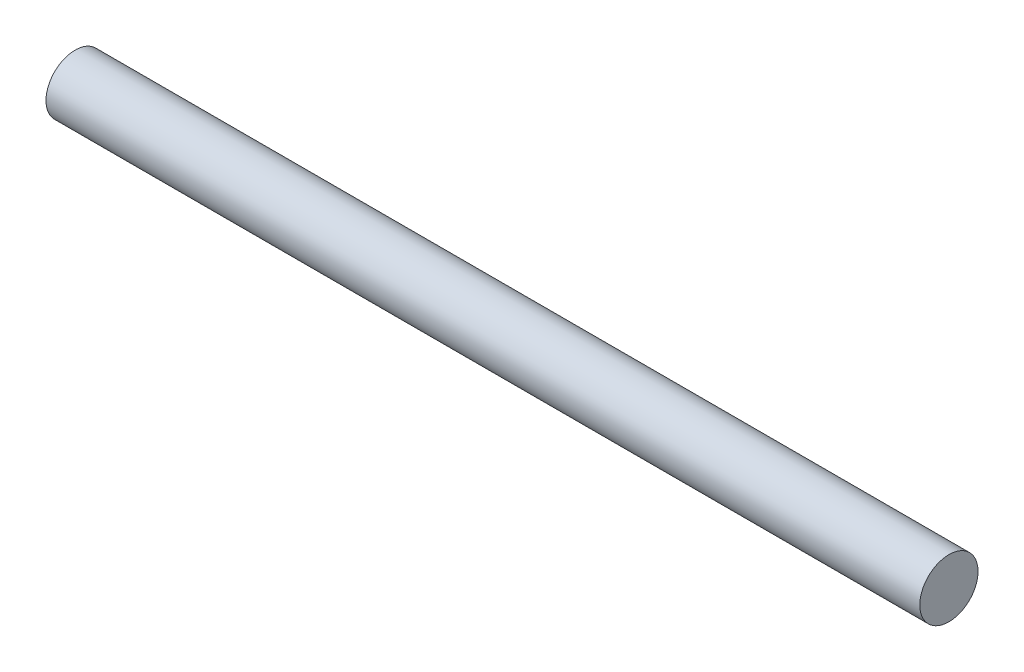
SolidWorks part; units mm, degrees
ref_plane "Front Plane" through (0, 0, 0) normal (0, 0, 1) x (1, 0, 0)
ref_plane "Top Plane" through (0, 0, 0) normal (0, 1, 0) x (1, 0, 0)
ref_plane "Right Plane" through (0, 0, 0) normal (1, 0, 0) x (0, 0, -1)
sketch "Sketch1" plane through (0, 0, 0) normal (1, 0, 0) x (0, 0, -1)
  circle A0 centre (0, 0) radius 1.5
  dimension "D1" = 3
extrude "Boss-Extrude1" add sketch "Sketch1" along normal blind 45
